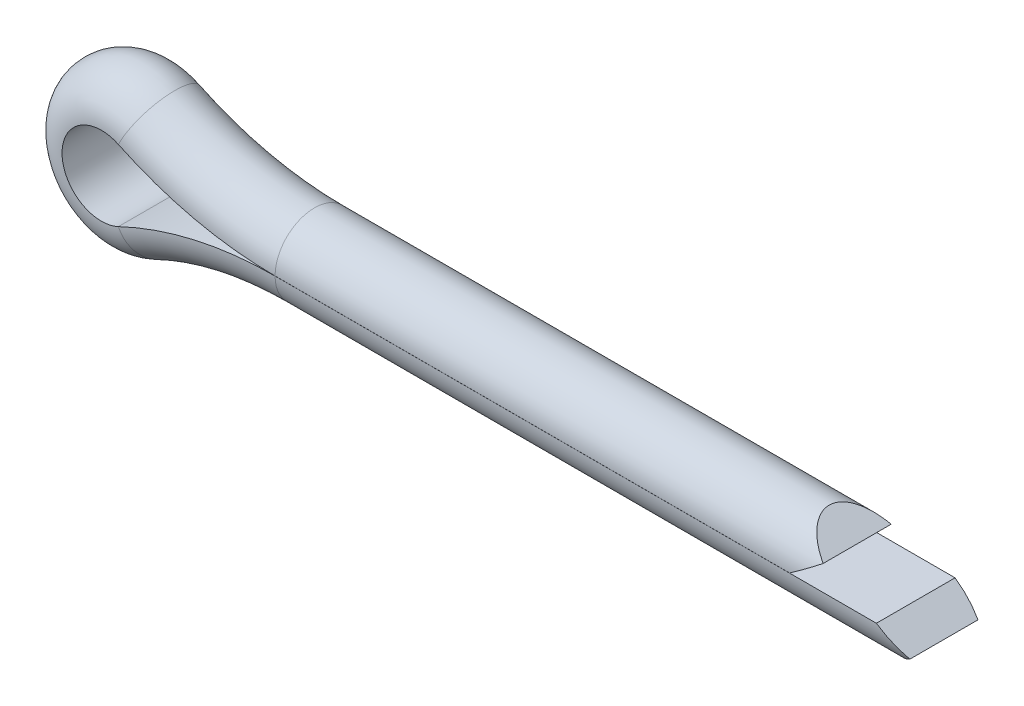
SolidWorks part; units mm, degrees
ref_plane "Front Plane" through (0, 0, 0) normal (0, 0, 1) x (1, 0, 0)
ref_plane "Top Plane" through (0, 0, 0) normal (0, 1, 0) x (1, 0, 0)
ref_plane "Right Plane" through (0, 0, 0) normal (1, 0, 0) x (0, 0, -1)
sketch "PathSke" plane through (0, 0, 0) normal (0, 0, 1) x (1, 0, 0)
  line L0 (0, 0) -> (38.8652, 0) construction
  line L1 (0, 0) -> (0, 12.2501) construction
  line L2 (6.4, 0) -> (6.4, 12.2501) construction
  line L3 (6.4, 1.45) -> (26.4, 1.45)
  line L4 (6.4, -1.45) -> (29.6, -1.45)
  arc A0 (1.2499, 2.6168) -> (1.2499, -2.6168) centre (0, 0) ccw
  arc A1 (6.4, 1.45) -> (1.2499, 2.6168) centre (6.4, 13.3991) cw
  arc A2 (6.4, -1.45) -> (1.2499, -2.6168) centre (6.4, -13.3991) ccw
  dimension "Diameter" = 2.9
ref_plane "SectionPlane" through (26.4, 1.45, 0) normal (1, 0, 0) x (0, 0, -1)
sketch "SectionSke" plane through (26.4, 1.45, 0) normal (1, 0, 0) x (0, 0, -1)
  line L0 (0, -1.45) -> (0, 8.6928) construction
  line L1 (0, -1.45) -> (0, 10.8001) construction
  line L2 (-1.45, -1.45) -> (1.45, -1.45) construction
  line L3 (-1.45, -1.448) -> (1.45, -1.448)
  arc A0 (1.45, -1.448) -> (-1.45, -1.448) centre (0, -1.45) ccw
  dimension "D1" = 0.002
  dimension "Diameter" = 2.9
sweep "BaseBody" add profiles "SectionSke" path "PathSke"
sketch "ConeCutSke" plane through (0, 0, 0) normal (0, 0, 1) x (1, 0, 0)
  line L0 (0, 0) -> (34.6884, 0) construction
  line L1 (25.3575, 1.46) -> (29.61, 1.46)
  line L2 (29.61, 1.46) -> (29.61, -1.46)
  line L3 (26.4, 1.45) -> (6.4, 1.45) construction
  line L4 (25.3575, 1.46) -> (26.4, 0.726)
  line L5 (26.4, 0.002) -> (26.4, 1.45) construction
  line L6 (26.4, 0.726) -> (25.3575, 0)
  line L7 (25.3575, 0) -> (28.5575, 0)
  line L8 (28.5575, 0) -> (29.6, -0.726)
  line L9 (29.6, -1.45) -> (29.6, -0.002) construction
  line L10 (29.6, -0.726) -> (28.5575, -1.46)
  line L11 (28.5575, -1.46) -> (29.61, -1.46)
  point P19 (29.61, 0)
  dimension "D1" = 0.01
  dimension "D2" = 70
  dimension "D3" = 70
  dimension "D4" = 0.01
extrude "ConeCut" cut sketch "ConeCutSke" against normal through all and the other way through all
equation "\"Diameter@SectionSke\" = \"Diameter@PathSke\""
